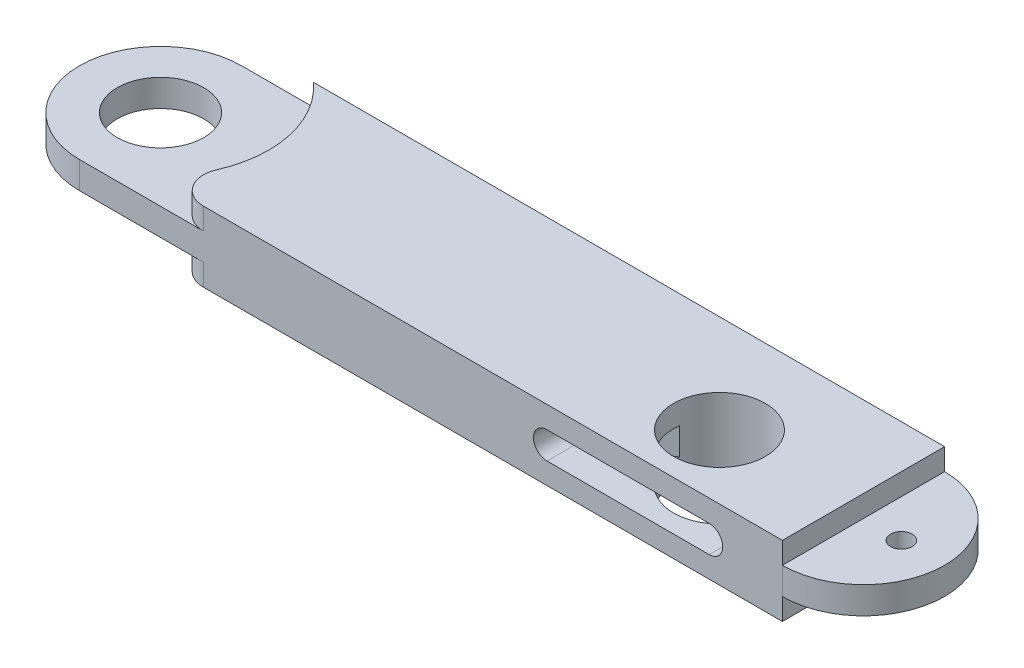
SolidWorks part; units mm, degrees
ref_plane "Front Plane" through (0, 0, 0) normal (0, 0, 1) x (1, 0, 0)
ref_plane "Top Plane" through (0, 0, 0) normal (0, 1, 0) x (1, 0, 0)
ref_plane "Right Plane" through (0, 0, 0) normal (1, 0, 0) x (0, 0, -1)
sketch "main" plane through (0, 0, 0) normal (0, 1, 0) x (1, 0, 0)
  line L0 (0, 0) -> (130, 0) construction
  line L1 (0, 15) -> (130, 15)
  line L2 (0, -15) -> (130, -15)
  arc A0 (0, 15) -> (0, -15) centre (0, 0) ccw
  arc A1 (130, -15) -> (130, 15) centre (130, 0) ccw
  circle A2 centre (0, 0) radius 8
  point P3 (65, 0)
  point P8 (-15, 0)
  dimension "D3" = 16
  dimension "D1" = 130
  dimension "D2" = 15
extrude "Boss-Extrude1" add sketch "main" along normal blind 13
sketch "Sketch5" plane through (0, 13, 0) normal (0, 1, 0) x (1, 0, 0)
  line L0 (0, -15) -> (130, -15) construction
  line L1 (130, 15) -> (130, -15)
  arc A0 (130, 15) -> (130, -15) centre (130, 0) cw
  point P6 (145, 0)
  dimension "D1" = 30
  dimension "D2" = 15
extrude "Cut-Extrude5" cut sketch "Sketch5" against normal blind 4
sketch "Sketch6" plane through (0, 0, 0) normal (0, -1, 0) x (1, 0, 0)
  line L0 (130, -15) -> (0, -15) construction
  line L1 (130, 15) -> (130, -15)
  arc A0 (130, 15) -> (130, -15) centre (130, 0) cw
  point P6 (145, 0)
  dimension "D1" = 30
  dimension "D2" = 15
extrude "Cut-Extrude6" cut sketch "Sketch6" against normal blind 4
sketch "joint hole" plane through (0, 0, 0) normal (0, -1, 0) x (1, 0, 0)
  circle A0 centre (106.4985, 3.1366) radius 8.5
  dimension "D1" = 17
extrude "Cut-Extrude7" cut sketch "joint hole" against normal blind 13
sketch "cut_out joint" plane through (0, 0, 15) normal (0, 0, 1) x (1, 0, 0)
  line L0 (86.4681, 6.4449) -> (116.4681, 6.4449) construction
  line L1 (86.4681, 8.9449) -> (116.4681, 8.9449)
  line L2 (86.4681, 3.9449) -> (116.4681, 3.9449)
  arc A0 (86.4681, 8.9449) -> (86.4681, 3.9449) centre (86.4681, 6.4449) ccw
  arc A1 (116.4681, 3.9449) -> (116.4681, 8.9449) centre (116.4681, 6.4449) ccw
  point P2 (101.4681, 6.4449)
  dimension "D1" = 30
  dimension "D2" = 5
extrude "Cut-Extrude8" cut sketch "cut_out joint" against normal blind 9
sketch "Sketch9" plane through (0, 13, 0) normal (0, 1, 0) x (1, 0, 0)
  circle A0 centre (0, 0) radius 20.0142
extrude "Cut-Extrude9" cut sketch "Sketch9" against normal blind 4
sketch "Sketch10" plane through (0, 0, 0) normal (0, -1, 0) x (1, 0, 0)
  circle A0 centre (0, 0) radius 20.0142
  arc A1 (13.2502, -15) -> (13.2502, 15) centre (0, 0) ccw construction
  point P2 (0, 0)
extrude "Cut-Extrude10" cut sketch "Sketch10" against normal blind 4
fillet "Fillet1" radius 5 1 edges at (13.2502, 2, 15)
fillet "Fillet2" radius 5 1 edges at (13.2502, 11, 15)
sketch "Sketch11" plane through (0, 9, 0) normal (0, 1, 0) x (1, 0, 0)
  line L0 (130, 15) -> (130, -15) construction
  line L1 (130, -15) -> (137, 0)
  line L2 (137, 0) -> (130, 15)
  circle A0 centre (137, 0) radius 2
  dimension "D1" = 4
  dimension "D2" = 7
extrude "Cut-Extrude11" cut sketch "Sketch11" against normal blind 5 contours L1 A0 L2 | L2 A0 L1 region at (135.9347, 9, 0) region at (137.6019, 9, 0)
chamfer "Chamfer1" distance 7 angle 60 1 edges at (98.4953, 6.4449, 6) first distance on face at (106.4985, 0, -5.3634)
